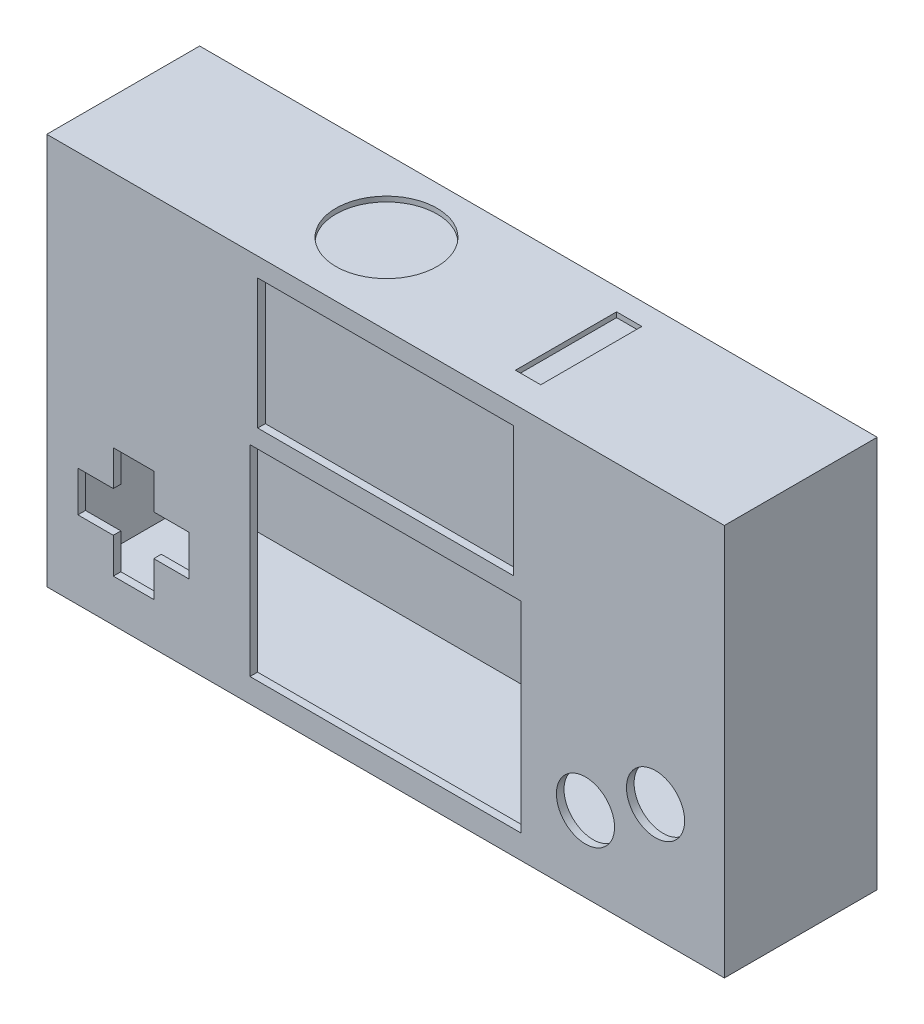
SolidWorks part; units mm, degrees
note: The reader was unsure of these and kept them because the rebuilt part matched: shared geometry of "Sketch1<3>", "Sketch1<4>", "Sketch1<5>", "Sketch1<6>".
ref_plane "Front Plane" through (0, 0, 0) normal (0, 0, 1) x (1, 0, 0)
ref_plane "Top Plane" through (0, 0, 0) normal (0, 1, 0) x (1, 0, 0)
ref_plane "Right Plane" through (0, 0, 0) normal (1, 0, 0) x (0, 0, -1)
sketch "Sketch1" plane through (0, 0, 0) normal (0, 0, 1) x (1, 0, 0)
  line L0 (-4, -4) -> (-11, -4)
  line L1 (115.34, 56.5974) -> (-15.66, 56.5974)
  line L2 (115.34, 56.5974) -> (115.34, -17.9026)
  line L3 (115.34, -17.9026) -> (-15.66, -17.9026)
  line L4 (-15.66, 56.5974) -> (-15.66, -17.9026)
  line L5 (49.84, -17.9026) -> (49.84, 56.5974) construction
  line L6 (115.34, 19.3474) -> (-15.66, 19.3474) construction
  line L7 (-11, -4) -> (-11, 4)
  line L8 (-11, 4) -> (-4, 4)
  line L9 (-4, 4) -> (-4, 11)
  line L10 (-4, 11) -> (4, 11)
  line L11 (4, 11) -> (4, 4)
  line L12 (4, 4) -> (11, 4)
  line L13 (11, 4) -> (11, -4)
  line L14 (11, -4) -> (4, -4)
  line L15 (4, -4) -> (4, -11)
  line L16 (4, -11) -> (-4, -11)
  line L17 (-4, -11) -> (-4, -4)
  line L18 (-3.5, 10.3) -> (-3.5, 3.7) construction
  line L19 (3.5, 3.7) -> (3.5, 10.3) construction
  line L20 (3.3, 10.5) -> (-3.3, 10.5) construction
  line L21 (-3.3, -10.5) -> (3.3, -10.5) construction
  line L22 (24.035, 24.0441) -> (24.035, 25.0441) construction
  line L23 (76.645, 25.0441) -> (23.035, 25.0441)
  line L24 (76.645, 25.0441) -> (76.645, -14.6759)
  line L25 (76.645, -14.6759) -> (23.035, -14.6759)
  line L26 (23.035, 25.0441) -> (23.035, -14.6759)
  line L27 (49.84, -14.6759) -> (49.84, 25.0441) construction
  line L28 (76.645, 5.1841) -> (23.035, 5.1841) construction
  line L29 (75.115, 54.3504) -> (24.565, 54.3504)
  line L30 (75.115, 54.3504) -> (75.115, 28.6454)
  line L31 (75.115, 28.6454) -> (24.565, 28.6454)
  line L32 (24.565, 54.3504) -> (24.565, 28.6454)
  line L33 (49.84, 28.6454) -> (49.84, 54.3504) construction
  line L34 (75.115, 41.4979) -> (24.565, 41.4979) construction
  line L35 (24.035, 24.0441) -> (23.035, 24.0441) construction
  line L36 (75.645, -13.6759) -> (76.645, -13.6759) construction
  line L37 (75.645, -13.6759) -> (75.645, -14.6759) construction
  line L38 (25.565, 29.6454) -> (25.565, 28.6454) construction
  line L39 (25.565, 29.6454) -> (24.565, 29.6454) construction
  line L40 (74.115, 53.3504) -> (74.115, 54.3504) construction
  line L41 (74.115, 53.3504) -> (75.115, 53.3504) construction
  line L42 (-15.16, 34.5974) -> (-15.66, 34.5974) construction
  line L43 (114.84, -17.4026) -> (114.84, -17.9026) construction
  line L44 (22.09, 56.5974) -> (22.09, 56.0974) construction
  line L45 (23.035, -14.6759) -> (23.035, -16.1759) construction
  line L46 (114.84, -17.4026) -> (115.34, -17.4026) construction
  line L47 (78.145, 26.5441) -> (21.535, 26.5441)
  line L48 (78.145, 26.5441) -> (78.145, -16.1759)
  line L49 (78.145, -16.1759) -> (21.535, -16.1759)
  line L50 (21.535, 26.5441) -> (21.535, -16.1759)
  line L51 (78.145, 26.5441) -> (21.535, -16.1759) construction
  line L52 (78.145, -16.1759) -> (21.535, 26.5441) construction
  line L53 (23.065, 55.8504) -> (76.615, 55.8504)
  line L54 (23.065, 55.8504) -> (23.065, 27.1454)
  line L55 (23.065, 27.1454) -> (76.615, 27.1454)
  line L56 (76.615, 55.8504) -> (76.615, 27.1454)
  line L57 (23.065, 55.8504) -> (76.615, 27.1454) construction
  line L58 (23.065, 27.1454) -> (76.615, 55.8504) construction
  line L59 (23.035, -14.6759) -> (21.535, -14.6759) construction
  line L60 (24.565, 28.6454) -> (24.565, 27.1454) construction
  line L61 (24.565, 28.6454) -> (23.065, 28.6454) construction
  line L62 (115.34, -17.9026) -> (115.34, -19.4026) construction
  line L63 (-17.16, 58.0974) -> (116.84, 58.0974)
  line L64 (-17.16, 58.0974) -> (-17.16, -19.4026)
  line L65 (-17.16, -19.4026) -> (116.84, -19.4026)
  line L66 (116.84, 58.0974) -> (116.84, -19.4026)
  line L67 (-17.16, 58.0974) -> (116.84, -19.4026) construction
  line L68 (-17.16, -19.4026) -> (116.84, 58.0974) construction
  line L69 (115.34, -17.9026) -> (116.84, -17.9026) construction
  line L70 (76.645, 25.0441) -> (76.645, 26.5441) construction
  line L71 (76.645, 25.0441) -> (78.145, 25.0441) construction
  circle A0 centre (89.3755, -4.4426) radius 5.75
  circle A1 centre (103.2319, 3.5574) radius 5.75
  arc A3 (89.7399, -4.3784) -> (89.0112, -4.5069) centre (89.3755, -4.4426) ccw construction
  arc A4 (103.5963, 3.6216) -> (102.8676, 3.4931) centre (103.2319, 3.5574) ccw construction
  arc A5 (84.2053, -5.3543) -> (90.2872, -9.6129) centre (89.3755, -4.4426) ccw construction
  point P0 (49.84, 19.3474)
  point P31 (49.84, 41.4979)
  point P39 (49.84, 5.1841)
  point P59 (49.84, 5.1841)
  point P68 (49.84, 41.4979)
  point P79 (49.84, 19.3474)
  dimension "D5" = 0.5
  dimension "D1" = 0.5
  dimension "D2" = 0.5
  dimension "D3" = 0.5
  dimension "D4" = 0.5
  dimension "D6" = 1
  dimension "D7" = 1
  dimension "D8" = 0.5
  dimension "D9" = 1.5
  dimension "D10" = 1.5
  dimension "D11" = 1.5
extrude "Boss-Extrude1" add sketch "Sketch1" along normal blind 1.5 contours L1 L4 L3 L2 A1 A0 L32 L29 L30 L31 L26 L23 L24 L25 L16 L17 L0 L7 L8 L9 L10 L11 L12 L13 L14 L15 | L47 L50 L49 L48 L26 L23 L24 L25 | L56 L53 L54 L55 L32 L29 L30 L31
extrude "Boss-Extrude2" add sketch "Sketch1<3>" against normal up to surface (0.0005 mm away) contours L47 L50 L49 L48 L26 L23 L24 L25
sketch "Sketch1<3>" plane through (0, 0, 0) normal (0, 0, 1) x (1, 0, 0) same geometry as "Sketch1"
extrude "Boss-Extrude3" add sketch "Sketch1<4>" against normal up to surface (0.0005 mm away) contours L56 L53 L54 L55 L32 L29 L30 L31
sketch "Sketch1<4>" plane through (0, 0, 0) normal (0, 0, 1) x (1, 0, 0) same geometry as "Sketch1"
extrude "Boss-Extrude4" add sketch "Sketch1<5>" along normal up to surface and the other way up to surface contours L66 L63 L64 L65 L4 L1 L2 L3
sketch "Sketch1<5>" plane through (0, 0, 0) normal (0, 0, 1) x (1, 0, 0) same geometry as "Sketch1"
extrude "Boss-Extrude5" add sketch "Sketch1<6>" against normal blind 1.5 from surface at -27.2345 contours L64 L65 L66 L63 starting at face at (49.84, 19.3474, -27.2345)
sketch "Sketch1<6>" plane through (0, 0, 0) normal (0, 0, 1) x (1, 0, 0) same geometry as "Sketch1"
sketch "Sketch2" plane through (0, 58.0974, 0) normal (0, 1, 0) x (1, 0, 0)
  line L1 (69.59, 4.4345) -> (74.59, 4.4345)
  line L2 (69.59, 4.4345) -> (69.59, 24.4345)
  line L3 (69.59, 24.4345) -> (74.59, 24.4345)
  line L4 (74.59, 4.4345) -> (74.59, 24.4345)
  circle A0 centre (34.09, 14.4345) radius 10
  circle A2 centre (34.09, 14.4345) radius 10 construction
  point P7 (0, 0)
  point P8 (74.59, 24.4345)
  point P9 (69.59, 4.4345)
  point P10 (1.1046, 14.4345)
  point P14 (0, 0)
  point P15 (0, 0)
  point P16 (0, 0)
extrude "Cut-Extrude1" cut sketch "Sketch2" against normal blind 1
